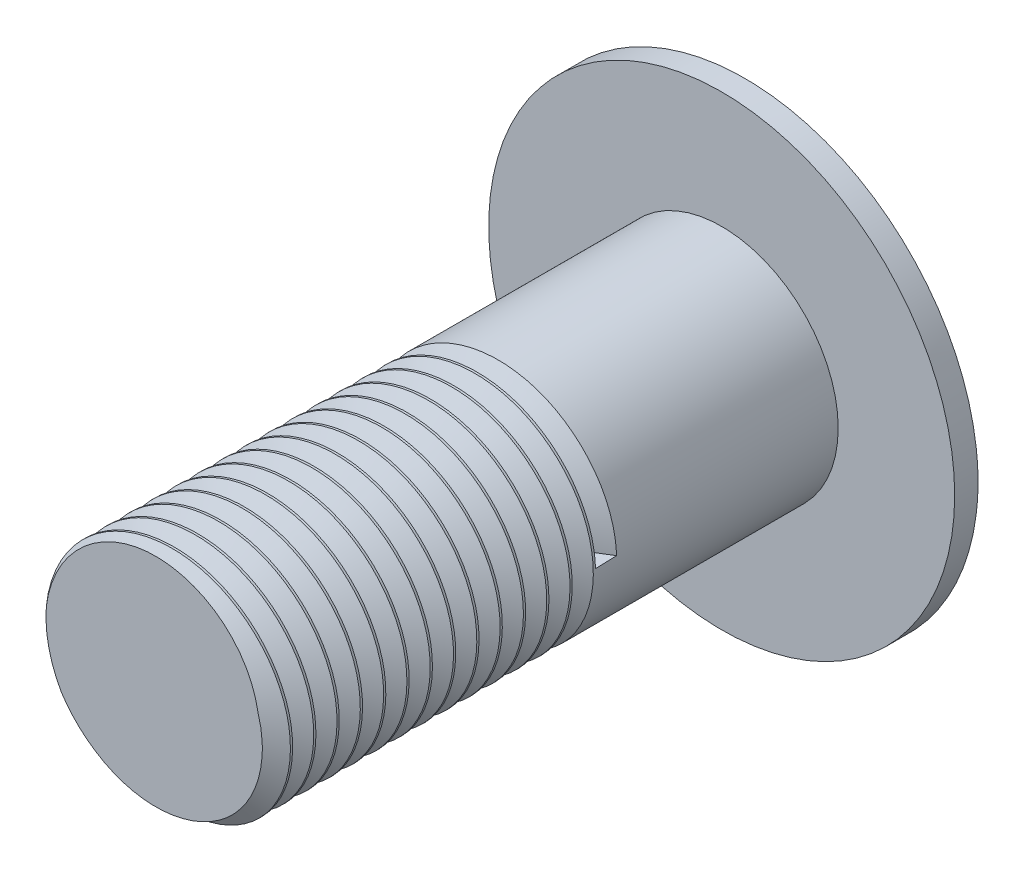
SolidWorks part; units mm, degrees
ref_plane "Front" through (0, 0, 0) normal (0, 0, 1) x (1, 0, 0)
ref_plane "Top" through (0, 0, 0) normal (0, 1, 0) x (1, 0, 0)
ref_plane "Right" through (0, 0, 0) normal (1, 0, 0) x (0, 0, -1)
sketch "Sketch1" plane through (0, 0, 0) normal (0, 0, 1) x (1, 0, 0)
  circle A0 centre (0, 0) radius 2.5
  dimension "D1" = 5
extrude "Boss-Extrude1" add sketch "Sketch1" along normal blind 12
sketch "Sketch2" plane through (0, 0, 0) normal (1, 0, 0) x (0, 0, -1)
  line L0 (0, 0) -> (6.4557, 0) construction
  line L1 (0, 0) -> (0, 5)
  line L2 (0, 5) -> (0.5, 5)
  line L3 (1.8278, 0.693) -> (1.8278, -0.693) construction
  line L4 (0, 0) -> (1.8278, 0)
  spline S0 degree 3 poles (1.8278, 0) (1.8278, 1.8301) (1.5196, 3.4287) (0.5, 5) knots 0 0 0 0 1 1 1 1
  dimension "D1" = 5
  dimension "D2" = 0.5
revolve "Revolve2" add sketch "Sketch2" angle 360 about L4
sketch "Sketch3" plane through (0, 0, 0) normal (0, 0, 1) x (1, 0, 0)
  line L0 (0, 0) -> (6.0499, 0) construction
  line L2 (5.4741, -0.625) -> (-5.5577, -0.625)
  line L3 (5.4741, -0.625) -> (5.4741, 0.625)
  line L4 (5.4741, 0.625) -> (-5.5577, 0.625)
  line L5 (-5.5577, -0.625) -> (-5.5577, 0.625)
  point P7 (5.4741, 0)
  dimension "D1" = 1.25
ref_plane "Plane1" through (0, 0, -0.5) normal (0, 0, 1) x (1, 0, 0)
sketch "Sketch4" plane through (0, 0, -0.5) normal (0, 0, 1) x (1, 0, 0)
  line L4 (-5.5577, -0.625) -> (5.4741, -0.625)
  line L5 (-5.5577, 0.625) -> (-5.5577, -0.625)
  line L6 (5.4741, 0.625) -> (-5.5577, 0.625)
  line L7 (5.4741, -0.625) -> (5.4741, 0.625)
  line L8 (-5.5577, -0.625) -> (5.4741, -0.625)
  line L9 (-5.5577, 0.625) -> (-5.5577, -0.625)
  line L10 (5.4741, 0.625) -> (-5.5577, 0.625)
  line L11 (5.4741, -0.625) -> (5.4741, 0.625)
  dimension "D1" = 0
extrude "Cut-Extrude1" cut sketch "Sketch4" against normal blind 2
sketch "Sketch5" plane through (0, 0, 12) normal (0, 0, 1) x (1, 0, 0)
  circle A0 centre (0, 0) radius 2.5 construction
  circle A1 centre (0, 0) radius 2.5
curve "Helix/Spiral1" pitch 0.5 height 7 radius 2.5 centre (0, 0, 12) axis (0, 0, -1) start towards (1, 0, 0)
ref_plane "Plane2" through (2.5, 0, 12) normal (0, -0.9995, -0.0318) x (-1, 0, 0)
sketch "Sketch6" plane through (2.5, 0, 12) normal (0, -0.9995, -0.0318) x (-1, 0, 0)
  line L1 (0.3919, 0.0178) -> (-0.0238, 0.2578)
  line L2 (-0.0238, 0.2578) -> (-0.0238, -0.2222)
  line L3 (-0.0238, -0.2222) -> (0.3919, 0.0178)
  circle A0 centre (0.1148, 0.0178) radius 0.1386 construction
  point P1 (0.1148, 0.0178)
  dimension "D1" = 0.48
sweep "Cut-Sweep1" cut profiles "Sketch6" path "Helix/Spiral1" align with end faces yes
